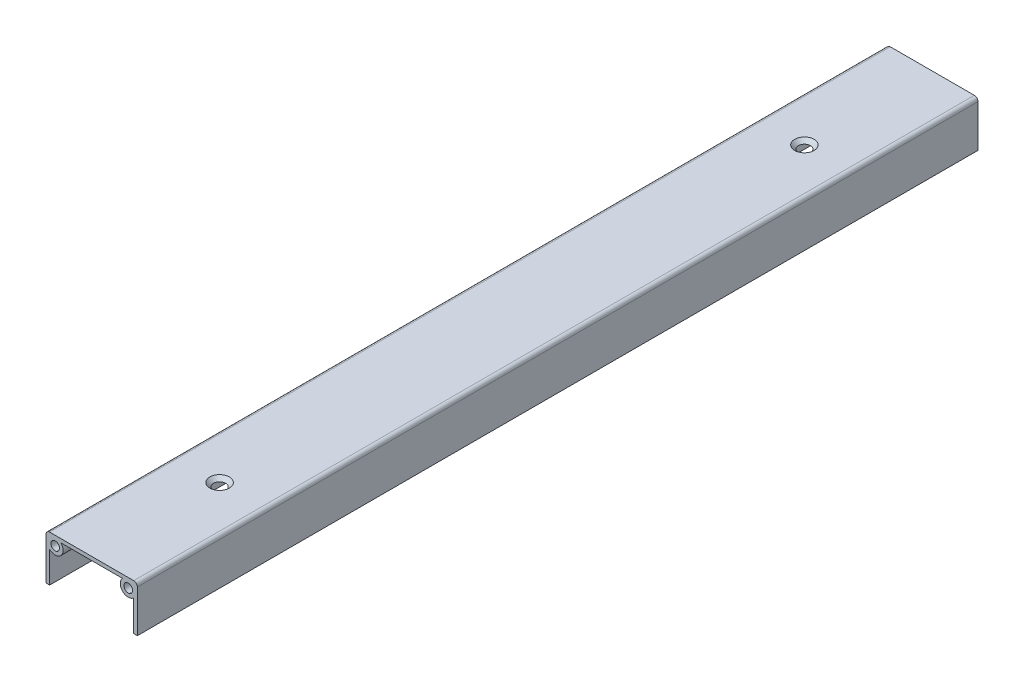
SolidWorks part; units mm, degrees
ref_plane "Front Plane" through (0, 0, 0) normal (0, 0, 1) x (1, 0, 0)
ref_plane "Top Plane" through (0, 0, 0) normal (0, 1, 0) x (1, 0, 0)
ref_plane "Right Plane" through (0, 0, 0) normal (1, 0, 0) x (0, 0, -1)
sketch "Sketch1" plane through (0, 0, 0) normal (0, 0, 1) x (1, 0, 0)
  line L0 (0, 31.75) -> (0, -31.75) construction
  line L1 (-31.75, -31.75) -> (31.75, -31.75)
  line L2 (-31.75, -31.75) -> (-31.75, 31.75)
  line L3 (-31.75, 31.75) -> (31.75, 31.75)
  line L4 (31.75, -31.75) -> (31.75, 31.75)
  line L5 (-31.75, -31.75) -> (31.75, 31.75) construction
  line L6 (-31.75, 31.75) -> (31.75, -31.75) construction
  line L7 (-31.75, 0) -> (31.75, 0) construction
  circle A0 centre (-25.4, 25.4) radius 3
  circle A1 centre (25.4, -25.4) radius 3
  circle A2 centre (-25.4, -25.4) radius 3
  circle A3 centre (25.4, 25.4) radius 3
  point P0 (0, 0)
  dimension "D3" = 6
  dimension "D9" = 50.8
  dimension "D4" = 50.8
  dimension "D1" = 63.5
  dimension "D2" = 63.5
  dimension "D5" = 6.35
extrude "Boss-Extrude1" add sketch "Sketch1" along normal mid plane 584.2
fillet "Fillet1" radius 2.54 4 edges at (-31.75, -31.75, 0) (31.75, -31.75, 0) (-31.75, 31.75, 0) (31.75, 31.75, 0)
shell "Shell1" thickness 2.54 removed face at (-28.4, -25.4, -292.1) removed face at (0, 0, 292.1)
sketch "Sketch3" plane through (0, 0, 292.1) normal (0, 0, 1) x (1, 0, 0)
  line L1 (-31.75, 29.21) -> (-31.75, -29.21) construction
  line L2 (-31.75, -0.1289) -> (31.9153, -0.1289)
  line L3 (-31.75, -0.1289) -> (-31.75, -31.8789)
  line L4 (-31.75, -31.8789) -> (31.9153, -31.8789)
  line L5 (31.9153, -0.1289) -> (31.9153, -31.8789)
  dimension "D1" = 31.75
extrude "Cut-Extrude2" cut sketch "Sketch3" against normal through all
hole_wizard "CSK for M6 Hex Socket Countersunk Head Screw1" positions "Sketch9" profile "Sketch8" countersink size "M6" standard "Lanco STD" end condition through all
sketch "Sketch9" plane through (0, 31.75, 0) normal (0, 1, 0) x (1, 0, 0)
  line L0 (29.21, -292.1) -> (-29.21, -292.1) construction
  line L1 (21.3781, 292.1) -> (-21.3781, 292.1) construction
  point P0 (0, 203.2)
  point P2 (0, -203.2)
  point P7 (0, 292.1)
  dimension "D1" = 88.9
  dimension "D2" = 88.9
sketch "Sketch8" plane through (0, 31.75, -203.2) normal (1, 0, 0) x (0, 0, 1)
  line L0 (0, 0) -> (0, 31.8789)
  line L1 (0, 31.8789) -> (3.2, 31.8789)
  line L2 (3.2, 31.8789) -> (3.2, 3.55)
  line L3 (3.2, 3.55) -> (6.75, 0)
  line L5 (6.75, 0) -> (0, 0)
  line L6 (-3.2, 3.55) -> (-6.75, 0) construction
  line L11 (0, -6.35) -> (0, 107.95) construction
  dimension "Thru Hole Dia." = 6.4
  dimension "Thru Hole Depth" = 31.8789
  dimension "Near C'Sink Dia." = 13.5
  dimension "Near C'Sink Angle" = 90
equation "\"D1@Boss-Extrude1\" = \"robot_width@Chassis.SLDASM\" - 6in"
